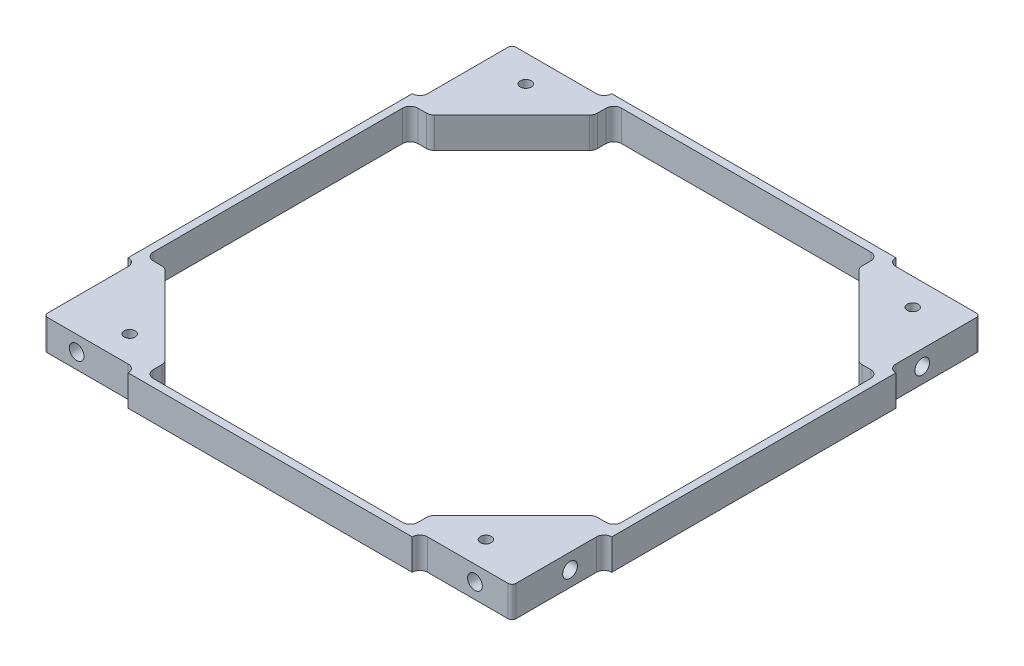
SolidWorks part; units mm, degrees
material "6061-T6 (SS)"
ref_plane "Front" through (0, 0, 0) normal (0, 0, 1) x (1, 0, 0)
ref_plane "Top" through (0, 0, 0) normal (0, 1, 0) x (1, 0, 0)
ref_plane "Right" through (0, 0, 0) normal (1, 0, 0) x (0, 0, -1)
sketch "Sketch10" plane through (0, 0, 0) normal (0, 1, 0) x (1, 0, 0)
  line L0 (29.365, -29.365) -> (46.415, -29.365) construction
  line L1 (50, -50) -> (-50, -50) construction
  line L2 (50, -50) -> (50, 50) construction
  line L3 (50, 50) -> (-50, 50) construction
  line L4 (-50, -50) -> (-50, 50) construction
  line L5 (50, -50) -> (-50, 50) construction
  line L6 (50, 50) -> (-50, -50) construction
  line L7 (48.415, -48.415) -> (29.365, -48.415)
  line L8 (48.415, -48.415) -> (48.415, -29.365)
  line L9 (48.415, 48.415) -> (29.365, 48.415)
  line L10 (-48.415, -48.415) -> (-48.415, -29.365)
  line L11 (48.415, -48.415) -> (-48.415, 48.415) construction
  line L12 (48.415, 48.415) -> (-48.415, -48.415) construction
  line L13 (29.365, -29.365) -> (-29.365, -29.365) construction
  line L14 (29.365, -29.365) -> (29.365, 29.365) construction
  line L15 (29.365, 29.365) -> (-29.365, 29.365) construction
  line L16 (-29.365, -27.365) -> (-29.365, 29.365) construction
  line L17 (29.365, -29.365) -> (-29.365, 29.365) construction
  line L18 (29.365, 29.365) -> (-29.365, -29.365) construction
  line L19 (119.2986, -29.365) -> (48.415, -29.365) construction
  line L20 (29.365, 29.365) -> (29.365, 46.415) construction
  line L21 (29.365, 68.7465) -> (29.365, 48.415) construction
  line L22 (-29.365, -27.365) -> (-29.365, 46.415) construction
  line L23 (-29.365, 75.7468) -> (-29.365, -27.365) construction
  line L24 (-29.365, 29.365) -> (-46.415, 29.365) construction
  line L25 (29.365, 29.365) -> (46.415, 29.365) construction
  line L38 (27.365, 48.415) -> (-27.365, 48.415)
  line L40 (-29.365, 48.415) -> (-48.415, 48.415)
  line L42 (-48.415, -27.365) -> (48.415, -27.365) construction
  line L44 (-29.365, 50) -> (-29.365, 48.415)
  line L46 (-1072.635, -27.365) -> (-50, -27.365) construction
  line L47 (-27.365, -1072.635) -> (-27.365, -50) construction
  line L48 (-1072.635, 27.365) -> (-50, 27.365) construction
  line L49 (27.365, -1072.635) -> (27.365, -50) construction
  line L50 (-27.365, -27.365) -> (27.365, 27.365) construction
  line L51 (-27.365, 27.365) -> (27.365, -27.365) construction
  line L52 (-46.415, -27.365) -> (-48.415, -27.365)
  line L53 (-50, -29.365) -> (-48.415, -29.365)
  line L54 (-48.415, -27.365) -> (-48.415, 27.365)
  line L56 (-48.415, -29.365) -> (-96.862, -29.365) construction
  line L58 (-27.365, -46.415) -> (-27.365, -48.415)
  line L59 (-29.365, -50) -> (-29.365, -77.4106) construction
  line L60 (-29.365, -48.415) -> (-48.415, -48.415)
  line L62 (-27.365, -48.415) -> (-27.365, 27.365) construction
  line L63 (-29.365, -48.415) -> (-29.365, -50)
  line L65 (-46.415, 27.365) -> (-48.415, 27.365)
  line L66 (-50, 29.365) -> (-98.3398, 29.365) construction
  line L67 (-27.365, 46.415) -> (-27.365, 48.415)
  line L68 (-48.415, 29.365) -> (-48.415, 48.415)
  line L69 (-48.415, 27.365) -> (27.365, 27.365) construction
  line L70 (-29.365, 48.415) -> (-29.365, 75.7468) construction
  line L71 (-29.365, 46.415) -> (-29.365, -27.365) construction
  line L73 (-48.415, 29.365) -> (-50, 29.365)
  line L74 (-50, 29.365) -> (-50, -29.365)
  line L76 (27.365, 46.415) -> (27.365, 48.415)
  line L77 (48.415, 29.365) -> (113.5851, 29.365) construction
  line L78 (46.415, 27.365) -> (48.415, 27.365)
  line L79 (48.415, 29.365) -> (48.415, 48.415)
  line L81 (29.365, 48.415) -> (29.365, 68.7465) construction
  line L82 (29.365, 46.415) -> (29.365, -29.365) construction
  line L83 (-29.365, 50) -> (29.365, 50)
  line L84 (29.365, 50) -> (29.365, 48.415)
  line L85 (48.415, 29.365) -> (50, 29.365)
  line L87 (50, 29.365) -> (50, -29.365)
  line L88 (50, -29.365) -> (48.415, -29.365)
  line L89 (46.415, -29.365) -> (-29.365, -29.365) construction
  line L90 (46.415, -27.365) -> (48.415, -27.365)
  line L91 (29.365, -48.415) -> (29.365, -74.3093) construction
  line L92 (48.415, -29.365) -> (119.2986, -29.365) construction
  line L93 (48.415, -27.365) -> (48.415, 27.365)
  line L94 (50, -27.365) -> (1072.635, -27.365) construction
  line L96 (27.365, -46.415) -> (27.365, -48.415)
  line L97 (27.365, -48.415) -> (-27.365, -48.415)
  line L98 (27.365, -48.415) -> (27.365, 27.365) construction
  line L99 (29.365, -48.415) -> (29.365, -50)
  line L100 (29.365, -50) -> (-29.365, -50)
  line L102 (-27.365, -46.415) -> (-27.365, -27.365)
  line L103 (-27.365, -27.365) -> (-46.415, -27.365)
  line L104 (-29.365, -48.415) -> (-29.365, -1141.245) construction
  line L105 (46.415, -27.365) -> (27.365, -27.365)
  line L106 (27.365, -27.365) -> (27.365, -46.415)
  line L107 (46.415, 27.365) -> (27.365, 27.365)
  line L108 (27.365, 27.365) -> (27.365, 46.415)
  line L109 (-27.365, 46.415) -> (-27.365, 27.365)
  line L110 (-27.365, 27.365) -> (-46.415, 27.365)
  point P0 (0, 0)
  point P6 (0, 0)
  point P11 (0, 0)
  point P36 (0, 0)
  dimension "D1" = 100
  dimension "D2" = 100
  dimension "D3" = 96.83
  dimension "D4" = 96.83
  dimension "D5" = 58.73
  dimension "D6" = 58.73
  dimension "D8" = 54.73
  dimension "D9" = 54.73
extrude "Boss-Extrude2" add sketch "Sketch10" along normal blind 6.35
fillet "Fillet7" radius 1.5875 8 edges at (-48.415, 3.175, 29.365) (-29.365, 3.175, 48.415) (29.365, 3.175, 48.415) (48.415, 3.175, 29.365) (48.415, 3.175, -29.365) (29.365, 3.175, -48.415) (-48.415, 3.175, -29.365) (-29.365, 3.175, -48.415)
fillet "Fillet8" radius 0.79 4 edges at (48.415, 3.175, -48.415) (48.415, 3.175, 48.415) (-48.415, 3.175, -48.415) (-48.415, 3.175, 48.415)
sketch "Sketch11" plane through (48.415, 0, 0) normal (1, 0, 0) x (0, 0, -1)
  line L0 (-48.415, 0) -> (-48.415, 6.35) construction
  line L1 (48.415, 6.35) -> (48.415, 0) construction
  line L2 (-47.625, 6.35) -> (-30.9525, 6.35) construction
  line L3 (-47.625, 0) -> (-30.9525, 0) construction
  line L4 (-36.415, 6.35) -> (-36.415, 0) construction
  line L5 (36.415, 6.35) -> (36.415, 0) construction
  line L6 (30.9525, 6.35) -> (47.625, 6.35) construction
  line L7 (30.9525, 0) -> (47.625, 0) construction
  point P0 (-36.415, 3.175)
  point P1 (36.415, 3.175)
  dimension "D1" = 12
  dimension "D2" = 12
hole_wizard "Tap Drill for #4 Helicoil5" positions "Sketch12" profile "Sketch13" hole size "#4-40" standard "ANSI Inch"
sketch "Sketch12" plane through (48.415, 0, 0) normal (1, 0, 0) x (0, 0, -1)
  point P0 (-36.415, 3.175)
  point P3 (36.415, 3.175)
sketch "Sketch13" plane through (48.415, 3.175, 36.415) normal (0, 1, 0) x (0, 0, -1)
  line L0 (0, 0) -> (0, 6.6053)
  line L1 (0, 6.6053) -> (1.524, 5.6896)
  line L2 (1.524, 5.6896) -> (1.524, 0)
  line L5 (1.524, 0) -> (0, 0)
  line L10 (0, 6.6053) -> (-1.524, 5.6896) construction
  line L11 (0, -6.35) -> (0, 107.95) construction
  dimension "Hole Dia." = 3.048
  dimension "Hole Depth" = 5.6896
  dimension "Drill Angle" = 118
sketch "Sketch15" plane through (0, 0, 48.415) normal (0, 0, 1) x (1, 0, 0)
  line L0 (-41.615, 6.35) -> (-41.615, 0) construction
  line L1 (-47.625, 6.35) -> (-30.9525, 6.35) construction
  line L2 (40.755, 6.35) -> (40.755, 0) construction
  line L3 (48.415, 6.35) -> (48.415, 0) construction
  line L4 (-48.415, 0) -> (-48.415, 6.35) construction
  line L7 (30.9525, 6.35) -> (47.625, 6.35) construction
  line L8 (30.9525, 0) -> (47.625, 0) construction
  point P8 (-41.615, 3.175)
  point P9 (40.755, 3.175)
  dimension "D1" = 6.8
  dimension "D2" = 7.66
  dimension "D3" = 3.175
hole_wizard "Tap Drill for #4 Helicoil5" positions "Sketch16" profile "Sketch17" hole size "#4-40" standard "ANSI Inch"
sketch "Sketch16" plane through (0, 0, 48.415) normal (0, 0, 1) x (1, 0, 0)
  point P0 (40.755, 3.175)
  point P3 (-41.615, 3.175)
sketch "Sketch17" plane through (40.755, 3.175, 48.415) normal (1, 0, 0) x (0, -1, 0)
  line L0 (0, 0) -> (0, 6.6053)
  line L1 (0, 6.6053) -> (1.524, 5.6896)
  line L2 (1.524, 5.6896) -> (1.524, 0)
  line L5 (1.524, 0) -> (0, 0)
  line L10 (0, 6.6053) -> (-1.524, 5.6896) construction
  line L11 (0, -6.35) -> (0, 107.95) construction
  dimension "Hole Dia." = 3.048
  dimension "Hole Depth" = 5.6896
  dimension "Drill Angle" = 118
fillet "Fillet10" radius 1.5875 8 edges at (-27.365, 3.175, -48.415) (-48.415, 3.175, -27.365) (48.415, 3.175, -27.365) (27.365, 3.175, -48.415) (-48.415, 3.175, 27.365) (-27.365, 3.175, 48.415) (27.365, 3.175, 48.415) (48.415, 3.175, 27.365)
sketch "Sketch18" plane through (0, 6.35, 0) normal (0, 1, 0) x (1, 0, 0)
  line L0 (45.085, 0) -> (-45.085, 0) construction
  line L5 (45.085, -47.9425) -> (-45.085, -47.9425) construction
  line L6 (45.085, -47.9425) -> (45.085, 47.9425) construction
  line L7 (45.085, 47.9425) -> (-45.085, 47.9425) construction
  line L8 (-45.085, -47.9425) -> (-45.085, 47.9425) construction
  line L9 (45.085, -47.9425) -> (-45.085, 47.9425) construction
  line L10 (45.085, 47.9425) -> (-45.085, -47.9425) construction
  line L11 (0, -47.9425) -> (0, 47.9425) construction
  line L12 (40.005, 0) -> (40.005, 42.8625) construction
  line L13 (37.465, 0) -> (37.465, -42.8625) construction
  point P0 (0, 0)
  point P19 (-36.195, -42.8625)
  point P20 (37.465, -42.8625)
  point P21 (40.005, 42.8625)
  point P22 (-40.005, 42.8625)
  dimension "D1" = 95.885
  dimension "D2" = 90.17
  dimension "D3" = 85.09
  dimension "D4" = 82.55
  dimension "D5" = 5.08
  dimension "D6" = 5.08
  dimension "D7" = 5.08
  dimension "D8" = 5.08
  dimension "D9" = 8.89
  dimension "D10" = 5.08
hole_wizard "Tap Drill for #4-40 Tap1" positions "Sketch19" profile "Sketch20" hole size "#4-40" standard "ANSI Inch"
sketch "Sketch19" plane through (0, 6.35, 0) normal (0, 1, 0) x (1, 0, 0)
  point P16 (37.465, -42.8625)
  point P19 (40.005, 42.8625)
  point P22 (-40.005, 42.8625)
  point P25 (-36.195, -42.8625)
sketch "Sketch20" plane through (37.465, 6.35, 42.8625) normal (1, 0, 0) x (0, 0, 1)
  line L0 (0, 0) -> (0, 9.3292)
  line L1 (0, 9.3292) -> (1.1303, 8.65)
  line L2 (1.1303, 8.65) -> (1.1303, 0)
  line L5 (1.1303, 0) -> (0, 0)
  line L10 (0, 9.3292) -> (-1.1303, 8.65) construction
  line L11 (0, -6.35) -> (0, 107.95) construction
  dimension "Hole Dia." = 2.2606
  dimension "Hole Depth" = 8.65
  dimension "Drill Angle" = 118
chamfer "Chamfer1" distance 17 angle 45 4 edges at (27.365, 3.175, -27.365) (-27.365, 3.175, 27.365) (27.365, 3.175, 27.365) (-27.365, 3.175, -27.365)
fillet "Fillet11" radius 1.5875 8 edges at (44.365, 3.175, -27.365) (27.365, 3.175, -44.365) (-27.365, 3.175, -44.365) (-44.365, 3.175, -27.365) (-27.365, 3.175, 44.365) (-44.365, 3.175, 27.365) (27.365, 3.175, 44.365) (44.365, 3.175, 27.365)
sketch "Sketch21" plane through (0, 6.35, 0) normal (0, 1, 0) x (1, 0, 0)
  line L0 (37.465, 0) -> (37.465, -42.8625) construction
  line L1 (-45.085, -47.9425) -> (-45.085, 47.9425) construction
  text T0 "<r-90>1</r>"
  text T1 "<r-90>2</r>"
  text T2 "<r-90>3</r>"
  text T3 "<r-90>4</r>"
  point P2 (37.465, -36.5433)
  point P6 (-45.085, -35.865)
  point P10 (-45.085, 38.9413)
sketch "Sketch22" plane through (0, 0, -48.415) normal (0, 0, -1) x (-1, 0, 0)
  line L0 (-47.625, 3.175) -> (47.625, 3.175) construction
  line L1 (-47.625, 6.35) -> (-47.625, 0) construction
  line L2 (47.625, 0) -> (47.625, 6.35) construction
  line L4 (-48.415, 0) -> (-48.415, 6.35) construction
  line L5 (48.415, 6.35) -> (48.415, 0) construction
  point P6 (-36.415, 3.175)
  point P7 (36.415, 3.175)
  dimension "D1" = 12
  dimension "D2" = 12
hole_wizard "Tap Drill for #4 Helicoil6" positions "Sketch23" profile "Sketch24" hole size "#4-40" standard "ANSI Inch"
sketch "Sketch23" plane through (0, 0, -48.415) normal (0, 0, -1) x (-1, 0, 0)
  point P0 (36.415, 3.175)
  point P3 (-36.415, 3.175)
sketch "Sketch24" plane through (-36.415, 3.175, -48.415) normal (1, 0, 0) x (0, 1, 0)
  line L0 (0, 0) -> (0, 6.6053)
  line L1 (0, 6.6053) -> (1.524, 5.6896)
  line L2 (1.524, 5.6896) -> (1.524, 0)
  line L5 (1.524, 0) -> (0, 0)
  line L10 (0, 6.6053) -> (-1.524, 5.6896) construction
  line L11 (0, -6.35) -> (0, 107.95) construction
  dimension "Hole Dia." = 3.048
  dimension "Hole Depth" = 5.6896
  dimension "Drill Angle" = 118
sketch "Sketch25" plane through (-48.415, 0, 0) normal (-1, 0, 0) x (0, 0, 1)
  line L0 (-48.415, 0) -> (-48.415, 6.35) construction
  line L1 (-47.625, 6.35) -> (-30.9525, 6.35) construction
  line L2 (-47.625, 0) -> (-30.9525, 0) construction
  line L3 (-36.415, 6.35) -> (-36.415, 0) construction
  line L4 (36.415, 6.35) -> (36.415, 0) construction
  line L5 (30.9525, 6.35) -> (47.625, 6.35) construction
  line L6 (30.9525, 0) -> (47.625, 0) construction
  line L7 (48.415, 6.35) -> (48.415, 0) construction
  point P0 (-36.415, 3.175)
  point P17 (36.415, 3.175)
  point P18 (30.5442, 12.2127)
  point P19 (0, 0)
  dimension "D1" = 12
  dimension "7.66mm" = 12
hole_wizard "Tap Drill for #4 Helicoil7" positions "Sketch26" profile "Sketch27" hole size "#4-40" standard "ANSI Inch"
sketch "Sketch26" plane through (-48.415, 0, 0) normal (-1, 0, 0) x (0, 0, 1)
  point P0 (-36.415, 3.175)
  point P3 (36.415, 3.175)
sketch "Sketch27" plane through (-48.415, 3.175, -36.415) normal (0, 1, 0) x (0, 0, 1)
  line L0 (0, 0) -> (0, 6.6057)
  line L1 (0, 6.6057) -> (1.524, 5.69)
  line L2 (1.524, 5.69) -> (1.524, 0)
  line L5 (1.524, 0) -> (0, 0)
  line L10 (0, 6.6057) -> (-1.524, 5.69) construction
  line L11 (0, -6.35) -> (0, 107.95) construction
  dimension "Hole Dia." = 3.048
  dimension "Hole Depth" = 5.69
  dimension "Drill Angle" = 118
